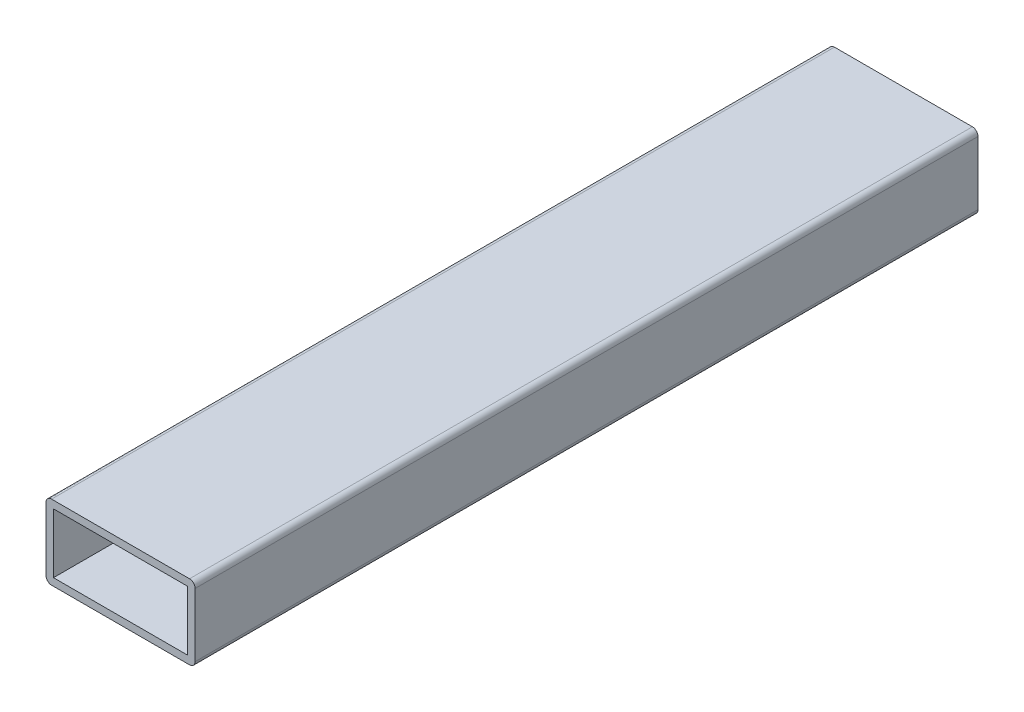
SolidWorks part; units mm, degrees
material "1.4000 (X6Cr13)"
ref_plane "Ön Düzlem" through (0, 0, 0) normal (0, 0, 1) x (1, 0, 0)
ref_plane "Üst Düzlem" through (0, 0, 0) normal (0, 1, 0) x (1, 0, 0)
ref_plane "Sağ Düzlem" through (0, 0, 0) normal (1, 0, 0) x (0, 0, -1)
sketch "Çizim1" plane through (0, 0, 0) normal (0, 0, 1) x (1, 0, 0)
  line L0 (-36, -16) -> (36, -16)
  line L1 (-37, 20) -> (37, 20)
  line L2 (-40, 17) -> (-40, -17)
  line L3 (-37, -20) -> (37, -20)
  line L4 (40, 17) -> (40, -17)
  line L5 (-40, 20) -> (40, -20) construction
  line L6 (-40, -20) -> (40, 20) construction
  line L7 (36, 16) -> (36, -16)
  line L8 (-36, 16) -> (36, 16)
  line L9 (-36, 16) -> (-36, -16)
  arc A0 (40, -17) -> (37, -20) centre (37, -17) cw
  arc A1 (37, 20) -> (40, 17) centre (37, 17) cw
  arc A2 (-37, 20) -> (-40, 17) centre (-37, 17) ccw
  arc A3 (-40, -17) -> (-37, -20) centre (-37, -17) ccw
  arc A4 (36, -16) -> (36, -16) centre (36, -16) cw
  arc A5 (36, 16) -> (36, 16) centre (36, 16) cw
  arc A6 (-36, 16) -> (-36, 16) centre (-36, 16) ccw
  arc A7 (-36, -16) -> (-36, -16) centre (-36, -16) ccw
  point P0 (0, 0)
  dimension "D3" = 3
  dimension "D1" = 80
  dimension "D2" = 40
  dimension "D4" = 4
extrude "Yükseklik-Ekstrüzyon1" add sketch "Çizim1" along normal blind 210 and the other way blind 210
